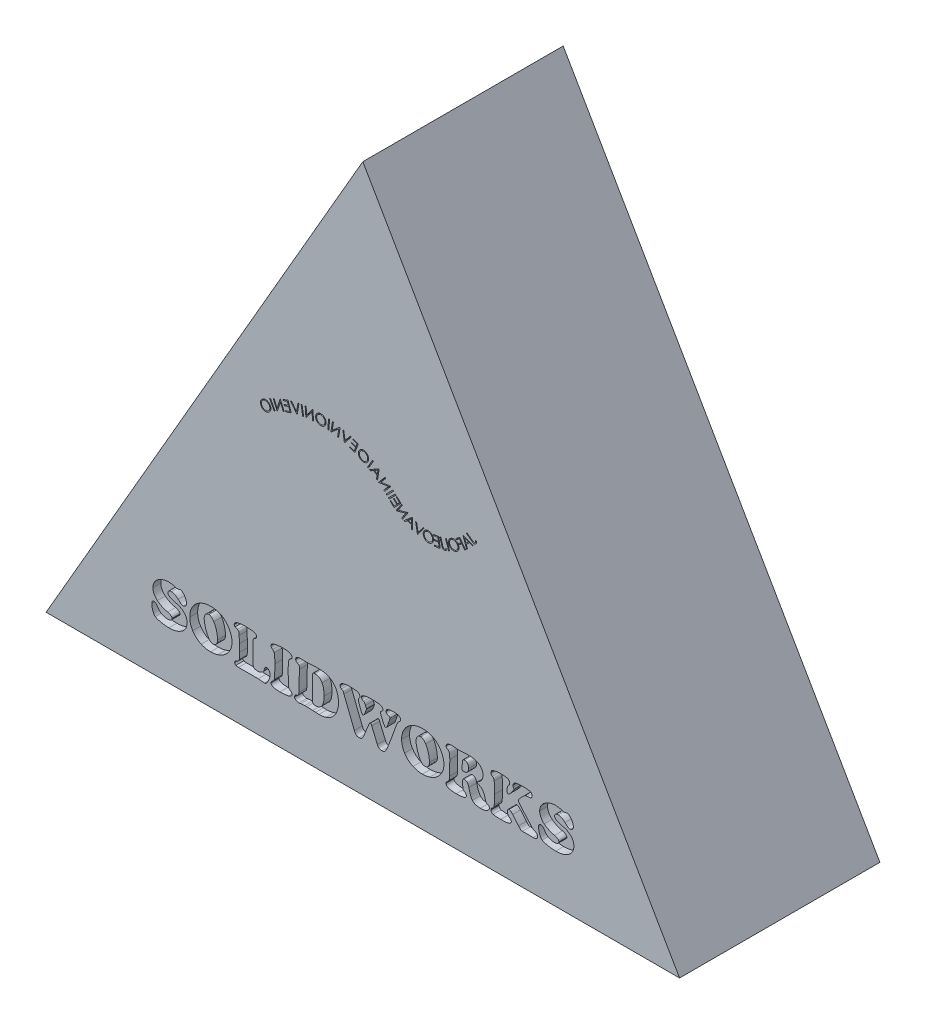
SolidWorks part; units mm, degrees
ref_plane "Front Plane" through (0, 0, 0) normal (0, 0, 1) x (1, 0, 0)
ref_plane "Top Plane" through (0, 0, 0) normal (0, 1, 0) x (1, 0, 0)
ref_plane "Right Plane" through (0, 0, 0) normal (1, 0, 0) x (0, 0, -1)
sketch "Sketch1" plane through (0, 0, 0) normal (0, 0, 1) x (1, 0, 0)
  line L0 (0, 0) -> (0, 117.3176) construction
  line L1 (0, 117.3176) -> (-101.6, -58.6588)
  line L2 (-101.6, -58.6588) -> (101.6, -58.6588)
  line L3 (101.6, -58.6588) -> (0, 117.3176)
  circle A0 centre (0, 0) radius 58.6588 construction
  dimension "D1" = 203.2
extrude "Boss-Extrude1" add sketch "Sketch1" along normal blind 64.262
sketch "Sketch2" plane through (0, 0, 64.262) normal (0, 0, 1) x (1, 0, 0)
  line L0 (-61.0626, 11.554) -> (61.0626, 11.554) construction
  line L1 (-76.2, -43.1092) -> (76.2, -43.1092) construction
  line L2 (0, 0) -> (0, 11.554) construction
  line L3 (0, 0) -> (0, -43.1092) construction
  line L4 (101.6, -58.6588) -> (0, 117.3176) construction
  line L5 (-76.2, -43.1092) -> (-76.2, -30.4092) construction
  line L6 (-76.2, -30.4092) -> (76.2, -30.4092) construction
  line L7 (76.2, -30.4092) -> (76.2, -43.1092) construction
  arc A0 (-35.0922, 29.037) -> (8.5374, 27.6476) centre (-13.9722, 6.5275) cw construction
  arc A1 (8.5374, 27.6476) -> (38.2722, 32.9276) centre (21.6833, 39.982) ccw construction
  text T0 "SOLIDWORKS" font "Cooper Black" height 12.7
  text T1 "JAFOIJEOVANEIINAIOEVNIONIVENIO"
  dimension "D1" = 12.7
  dimension "D2" = 152.4
extrude "Cut-Extrude1" cut sketch "Sketch2" against normal blind 2.54
